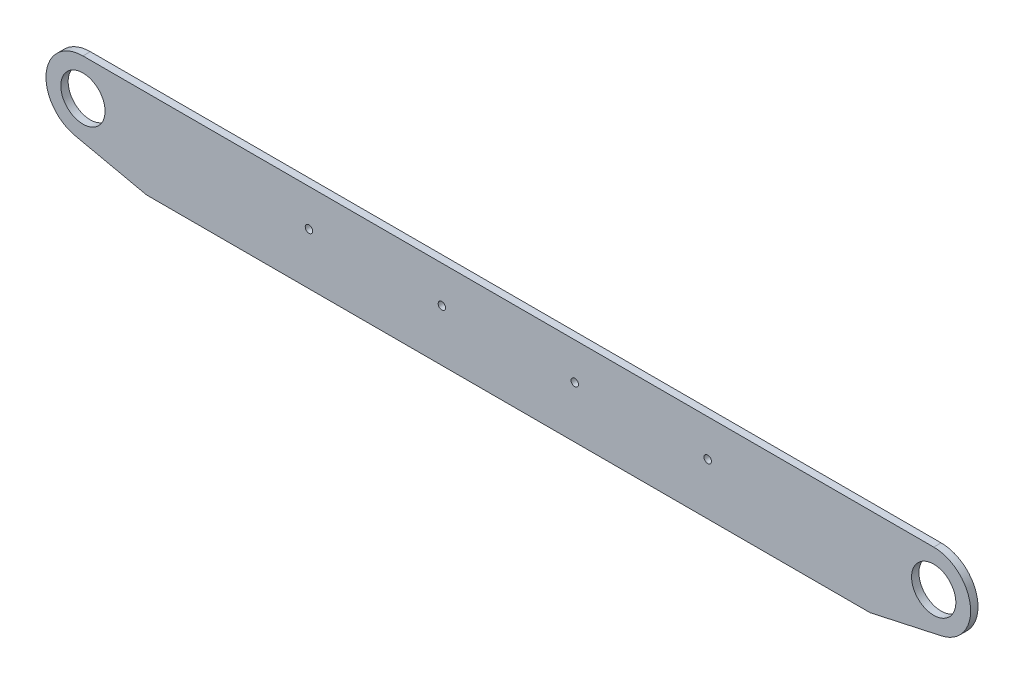
SolidWorks part; units mm, degrees
material "6061 Alloy"
ref_plane "Front Plane" through (0, 0, 0) normal (0, 0, 1) x (1, 0, 0)
ref_plane "Top Plane" through (0, 0, 0) normal (0, 1, 0) x (1, 0, 0)
ref_plane "Right Plane" through (0, 0, 0) normal (1, 0, 0) x (0, 0, -1)
sketch "Sketch1" plane through (0, 0, 457.2) normal (0, 0, 1) x (1, 0, 0)
  line L0 (311.15, 0) -> (311.15, 571.5) construction
  line L1 (-311.15, 609.6) -> (311.15, 609.6)
  line L2 (-311.15, 609.6) -> (-311.15, 533.4)
  line L3 (-311.15, 533.4) -> (311.15, 533.4)
  line L4 (311.15, 609.6) -> (311.15, 533.4)
  line L6 (311.15, 114.3) -> (-311.15, 114.3) construction
  dimension "D1" = 419.1
extrude "Boss-Extrude1" add sketch "Sketch1" along normal blind 6.35
sketch "Sketch2" plane through (0, 0, 463.55) normal (0, 0, 1) x (1, 0, 0)
  point P0 (171.45, 577.85)
hole_wizard "1/4 (0.25) Diameter Hole1" positions "Sketch2" profile "Sketch3" hole size "1/4" standard "ANSI Inch" end condition through all
sketch "Sketch3" plane through (171.45, 577.85, 463.55) normal (1, 0, 0) x (0, -1, 0)
  line L0 (0, 0) -> (0, 6.35)
  line L1 (0, 6.35) -> (3.175, 6.35)
  line L2 (3.175, 6.35) -> (3.175, 0)
  line L5 (3.175, 0) -> (0, 0)
  line L11 (0, -6.35) -> (0, 107.95) construction
  dimension "Thru Hole Dia." = 6.35
  dimension "Thru Hole Depth" = 6.35
pattern_linear "LPattern1" count 4 spacing 114.3 along (-1, 0, 0) of "1/4 (0.25) Diameter Hole1"
sketch "Sketch4" plane through (0, 0, 463.55) normal (0, 0, 1) x (1, 0, 0)
  line L0 (311.15, 533.4) -> (372.5878, 546.8327)
  line L1 (311.15, 609.6) -> (365.8062, 609.6)
  line L2 (311.15, 609.6) -> (311.15, 533.4)
  arc A0 (372.5878, 546.8327) -> (365.8062, 609.6) centre (365.8062, 577.85) ccw
  circle A1 centre (365.8062, 577.85) radius 19.05
  dimension "D1" = 63.5
  dimension "D2" = 38.1
extrude "Boss-Extrude3" add sketch "Sketch4" against normal up to surface (6.35 mm away) up to face at (60.325, 577.85, 457.2)
mirror "Mirror1" about plane through (0, 0, 0) normal (1, 0, 0) of "Boss-Extrude3"
